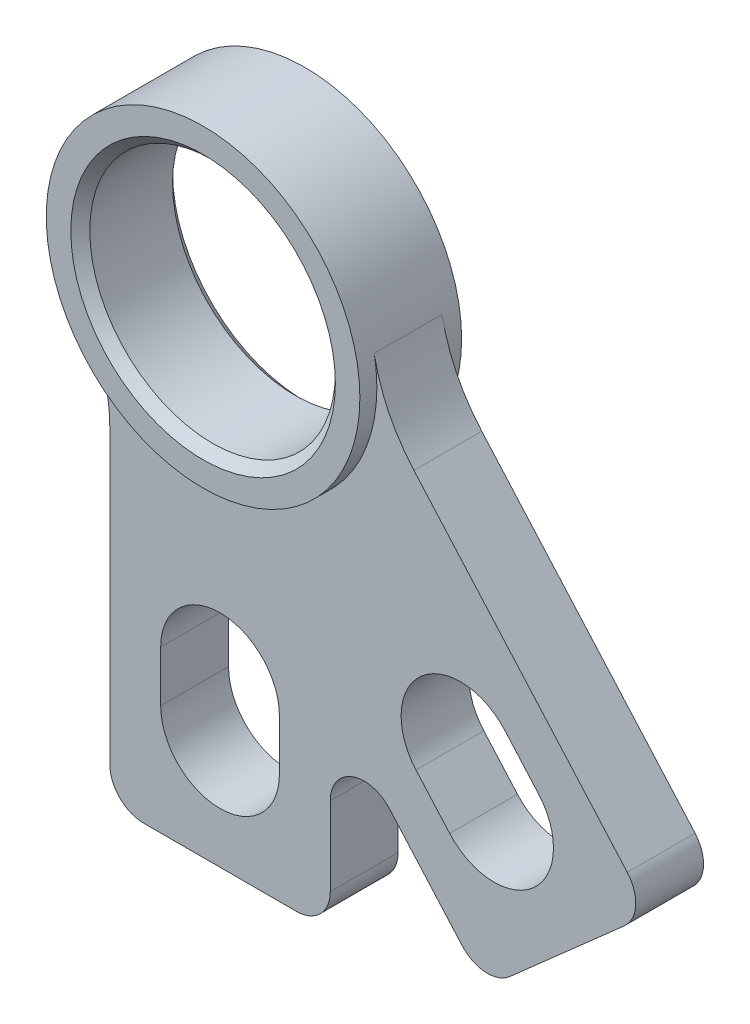
SolidWorks part; units mm, degrees
material "AISI 4130 Steel, annealed at 865C"
ref_plane "X-Y Datum" through (0, 0, 0) normal (0, 0, 1) x (1, 0, 0)
ref_plane "X-Z Datum" through (0, 0, 0) normal (0, 1, 0) x (1, 0, 0)
ref_plane "Y-Z Datum" through (0, 0, 0) normal (1, 0, 0) x (0, 0, -1)
sketch "Sketch1" plane through (0, 0, 0) normal (0, 0, 1) x (1, 0, 0)
  line L0 (0, -35.8956) -> (0, -31.1331) construction
  line L1 (-5.5562, -35.8956) -> (-5.5562, -31.1331)
  line L2 (5.5562, -35.8956) -> (5.5562, -31.1331)
  line L3 (25.6601, -29.0407) -> (22.5066, -25.4718) construction
  line L4 (21.4963, -32.7197) -> (18.3429, -29.1508)
  line L5 (29.8238, -25.3617) -> (26.6703, -21.7927)
  line L6 (-10.3187, -15.7343) -> (-10.3187, -46.2143)
  line L7 (-10.3187, -46.2143) -> (10.3187, -46.2143)
  line L10 (24.7599, -43.6058) -> (40.2252, -29.9408)
  line L11 (40.2252, -29.9408) -> (18.151, -4.9585)
  line L12 (10.3187, -46.2143) -> (10.3187, -27.2621)
  line L14 (0, -41.4518) -> (0, -46.2143) construction
  line L15 (29.3391, -33.2044) -> (32.4926, -36.7733) construction
  line L16 (28.2471, -23.5772) -> (31.816, -20.4237) construction
  line L17 (-5.5562, -33.5143) -> (-10.3187, -33.5143) construction
  line L18 (-10.3187, -20.8143) -> (10.3187, -20.8143) construction
  line L19 (10.3187, -20.8143) -> (10.3187, -46.2143) construction
  line L20 (5.5562, -33.5143) -> (10.3187, -33.5143) construction
  line L21 (0, -25.5768) -> (0, -20.8143) construction
  line L22 (24.7599, -43.6058) -> (7.9415, -24.5716) construction
  line L23 (7.9415, -24.5716) -> (23.4068, -10.9066) construction
  line L24 (19.9196, -30.9353) -> (16.3507, -34.0887) construction
  line L25 (18.8276, -21.308) -> (15.6741, -17.7391) construction
  line L29 (24.7599, -43.6058) -> (10.3187, -27.2621)
  line L33 (214.751, -243.0437) -> (0, 0) construction
  line L34 (0, -321.4016) -> (0, 0) construction
  circle A0 centre (0, 0) radius 11.4954
  arc A1 (-5.5562, -35.8956) -> (5.5562, -35.8956) centre (0, -35.8956) ccw
  arc A2 (5.5562, -31.1331) -> (-5.5562, -31.1331) centre (0, -31.1331) ccw
  arc A3 (21.4963, -32.7197) -> (29.8238, -25.3617) centre (25.6601, -29.0407) ccw
  arc A4 (26.6703, -21.7927) -> (18.3429, -29.1508) centre (22.5066, -25.4718) ccw
  arc A5 (14.4367, 2.6681) -> (-12.5852, -7.5598) centre (0, 0) ccw
  arc A6 (18.151, -4.9585) -> (14.4367, 2.6681) centre (30.0474, 5.5531) cw
  arc A7 (-10.3187, -15.7343) -> (-12.5852, -7.5598) centre (-26.1937, -15.7343) ccw
  arc A14 (-12.5852, -7.5598) -> (14.4367, 2.6681) centre (0, 0) ccw
  point P5 (0, -33.5143)
  point P11 (24.0833, -27.2562)
  point P24 (32.4926, -36.7733)
  point P39 (29.3391, -33.2044)
  dimension "D1" = 22.9908
  dimension "D2" = 14.6812
  dimension "D8" = 15.875
  dimension "D6" = 7.9375
  dimension "D7" = 5.08
  dimension "D3" = 20.6375
  dimension "D4" = 4.7625
  dimension "D5" = 25.4
extrude "Boss-Extrude2" add sketch "Sketch1" along normal mid plane 9.525 contours A5 A14 A0 region at (-5.05, 13.3422, 0)
extrude "Boss-Extrude3" add sketch "Sketch1<4>" along normal mid plane 6.35 contours L29 L10 L11 A6 A14 A7 L6 L7 A4 L5 A3 L4 A2 L2 A1 L1 region at (10.6657, -25.8814, 0)
sketch "Sketch1<4>" plane through (0, 0, 0) normal (0, 0, 1) x (1, 0, 0) same geometry as "Sketch1"
fillet "Fillet1" radius 3.175 5 edges at (-10.3187, -46.2143, 0) (40.2252, -29.9408, 0) (10.3187, -27.2621, 0) (24.7599, -43.6058, 0) (10.3187, -46.2143, 0)
sketch "Sketch4" plane through (0, 0, 4.7625) normal (0, 0, 1) x (1, 0, 0)
  point P0 (0, 0)
sketch "Sketch5" plane through (0, 0, -4.7625) normal (0, 0, -1) x (-1, 0, 0)
  point P0 (0, 0)
  point P1 (-28.1649, 3.919)
ref_point "Point1"
chamfer "Chamfer1" distance 0.889 angle 45 2 edges at (11.4954, 0, 4.7625) (11.4954, 0, -4.7625)
